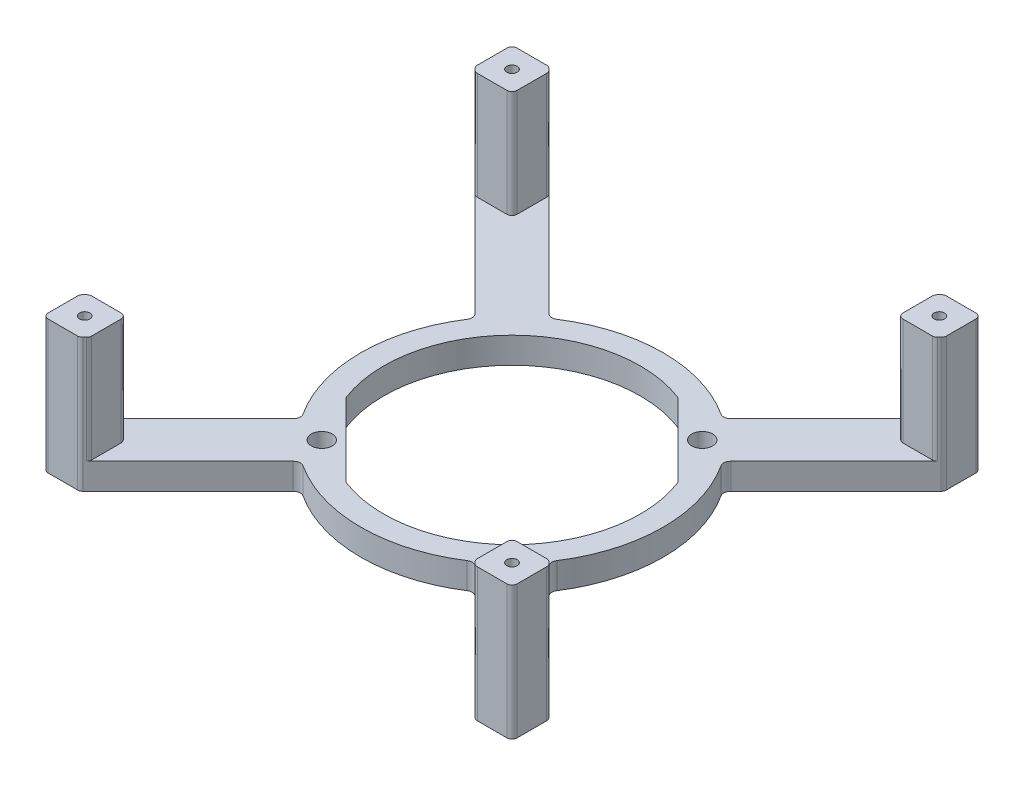
SolidWorks part; units mm, degrees
ref_plane "Front Plane" through (0, 0, 0) normal (0, 0, 1) x (1, 0, 0)
ref_plane "Top Plane" through (0, 0, 0) normal (0, 1, 0) x (1, 0, 0)
ref_plane "Right Plane" through (0, 0, 0) normal (1, 0, 0) x (0, 0, -1)
sketch "Sketch1" plane through (0, 0, 0) normal (0, 1, 0) x (1, 0, 0)
  line L0 (0, 50) -> (100, 50) construction
  line L1 (0, 0) -> (100, 0) construction
  line L2 (0, 0) -> (0, 100) construction
  line L3 (0, 100) -> (100, 100) construction
  line L4 (100, 0) -> (100, 100) construction
  line L5 (50, 0) -> (50, 50) construction
  line L6 (50, 50) -> (50, 100) construction
  line L7 (6, 95) -> (11.6569, 95)
  line L8 (5, 95) -> (95, 95) construction
  line L9 (50, 50) -> (110.8194, 110.8194) construction
  line L10 (50, 50) -> (-8.0727, 108.0727) construction
  line L11 (72.981, 58.8388) -> (58.8388, 72.981)
  line L12 (41.1612, 27.019) -> (27.019, 41.1612)
  line L13 (5, 95) -> (5, 5) construction
  line L14 (5, 5) -> (95, 5) construction
  line L15 (95, 95) -> (95, 5) construction
  line L16 (12.364, 94.7071) -> (32.5387, 74.5324)
  line L17 (5, 94) -> (5, 88.3431)
  line L18 (5.2929, 87.636) -> (25.4676, 67.4613)
  line L19 (50, 50) -> (0, 0) construction
  line L20 (95, 94) -> (95, 88.3431)
  line L21 (94.7071, 87.636) -> (74.5324, 67.4613)
  line L22 (94, 95) -> (88.3431, 95)
  line L23 (87.636, 94.7071) -> (67.4613, 74.5324)
  line L24 (50, 50) -> (108.0727, 108.0727) construction
  line L25 (94, 5) -> (88.3431, 5)
  line L26 (87.636, 5.2929) -> (67.4613, 25.4676)
  line L27 (95, 6) -> (95, 11.6569)
  line L28 (94.7071, 12.364) -> (74.5324, 32.5387)
  line L29 (50, 50) -> (108.0727, -8.0727) construction
  line L30 (5, 6) -> (5, 11.6569)
  line L31 (5.2929, 12.364) -> (25.4676, 32.5387)
  line L32 (6, 5) -> (11.6569, 5)
  line L33 (12.364, 5.2929) -> (32.5387, 25.4676)
  line L34 (50, 50) -> (-8.0727, -8.0727) construction
  arc A0 (58.8388, 72.981) -> (27.019, 41.1612) centre (50, 50) ccw
  arc A1 (41.1612, 27.019) -> (72.981, 58.8388) centre (50, 50) ccw
  arc A2 (25.6492, 65.7492) -> (25.6492, 34.2508) centre (50, 50) ccw
  arc A3 (11.6569, 95) -> (12.364, 94.7071) centre (11.6569, 94) cw
  arc A4 (6, 95) -> (5, 94) centre (6, 94) ccw
  arc A5 (5, 88.3431) -> (5.2929, 87.636) centre (6, 88.3431) ccw
  arc A6 (95, 88.3431) -> (94.7071, 87.636) centre (94, 88.3431) cw
  arc A7 (95, 94) -> (94, 95) centre (94, 94) ccw
  arc A8 (88.3431, 95) -> (87.636, 94.7071) centre (88.3431, 94) ccw
  arc A9 (88.3431, 5) -> (87.636, 5.2929) centre (88.3431, 6) cw
  arc A10 (94, 5) -> (95, 6) centre (94, 6) ccw
  arc A11 (95, 11.6569) -> (94.7071, 12.364) centre (94, 11.6569) ccw
  arc A12 (5, 11.6569) -> (5.2929, 12.364) centre (6, 11.6569) cw
  arc A13 (5, 6) -> (6, 5) centre (6, 6) ccw
  arc A14 (11.6569, 5) -> (12.364, 5.2929) centre (11.6569, 6) ccw
  arc A15 (65.7492, 74.3508) -> (34.2508, 74.3508) centre (50, 50) ccw
  arc A16 (74.3508, 34.2508) -> (74.3508, 65.7492) centre (50, 50) ccw
  arc A17 (34.2508, 25.6492) -> (65.7492, 25.6492) centre (50, 50) ccw
  arc A18 (74.5324, 32.5387) -> (74.3508, 34.2508) centre (75.5007, 33.5071) cw
  arc A19 (67.4613, 25.4676) -> (65.7492, 25.6492) centre (66.4929, 24.4993) ccw
  arc A20 (32.5387, 25.4676) -> (34.2508, 25.6492) centre (33.5071, 24.4993) cw
  arc A21 (25.4676, 32.5387) -> (25.6492, 34.2508) centre (24.4993, 33.5071) ccw
  arc A22 (25.4676, 67.4613) -> (25.6492, 65.7492) centre (24.4993, 66.4929) cw
  arc A23 (32.5387, 74.5324) -> (34.2508, 74.3508) centre (33.5071, 75.5007) ccw
  arc A24 (74.5324, 67.4613) -> (74.3508, 65.7492) centre (75.5007, 66.4929) ccw
  arc A25 (67.4613, 74.5324) -> (65.7492, 74.3508) centre (66.4929, 75.5007) cw
  point P27 (12.0711, 95)
  point P33 (5, 87.9289)
  point P72 (50, 50)
  point P86 (31.7496, 31.7496)
  point P87 (68.2504, 68.2504)
  dimension "D3" = 58
  dimension "D5" = 45
  dimension "D12" = 1
  dimension "D16" = 1.3694
  dimension "D1" = 100
  dimension "D2" = 100
  dimension "D4" = 5
  dimension "D6" = 45
  dimension "D7" = 5
  dimension "D8" = 20
  dimension "D9" = 10
  dimension "D10" = 22.5
  dimension "D11" = 5
  dimension "D13" = 10
  dimension "D14" = 5
  dimension "D17" = 25.81
  dimension "D15" = 4
extrude "Boss-Extrude1" add sketch "Sketch1" along normal blind 5
sketch "Sketch4" plane through (0, 5, 0) normal (0, 1, 0) x (1, 0, 0)
  line L0 (5.2929, 94.7071) -> (94.7071, 5.2929) construction
  line L1 (5.2929, 5.2929) -> (94.7071, 94.7071) construction
  arc A0 (94, 5) -> (95, 6) centre (94, 6) ccw construction
  arc A1 (6, 95) -> (5, 94) centre (6, 94) ccw construction
  arc A3 (5, 6) -> (6, 5) centre (6, 6) ccw construction
  arc A4 (95, 94) -> (94, 95) centre (94, 94) ccw construction
  point P3 (50, 50)
  point P17 (31.7496, 31.7496)
  point P18 (68.2504, 68.2504)
  dimension "D1" = 25.81
  dimension "D2" = 0
hole_wizard "Tap Drill for M4x0.7 Tap1" positions "3DSketch2" profile "Sketch5" hole size "M4x0.7" standard "ANSI Metric" end condition through all
sketch3d "3DSketch2"
  point P0 (31.7496, 5, -31.7496)
  point P3 (68.2504, 5, -68.2504)
sketch "Sketch5" plane through (31.7496, 5, -31.7496) normal (1, 0, 0) x (0, 0, 1)
  line L0 (0, 0) -> (0, 5)
  line L1 (0, 5) -> (2, 5)
  line L2 (2, 5) -> (2, 0)
  line L5 (2, 0) -> (0, 0)
  line L11 (0, -6.35) -> (0, 107.95) construction
  dimension "Thru Hole Dia." = 4
  dimension "Thru Hole Depth" = 5
sketch "Sketch6" plane through (0, 5, 0) normal (0, 1, 0) x (1, 0, 0)
  line L1 (6, 95) -> (11.6569, 95)
  line L2 (5, 94) -> (5, 88.3431)
  line L5 (11.6569, 95) -> (6, 95) construction
  line L6 (5, 94) -> (5, 88.3431) construction
  line L7 (13, 93.6569) -> (13, 88)
  line L8 (12, 87) -> (6.3431, 87)
  line L9 (5.636, 87.2929) -> (5.2929, 87.636)
  line L10 (5.2929, 87.636) -> (25.4676, 67.4613) construction
  line L11 (12.7071, 94.364) -> (12.364, 94.7071)
  line L12 (32.5387, 74.5324) -> (12.364, 94.7071) construction
  arc A0 (5.2929, 87.636) -> (5, 88.3431) centre (6, 88.3431) cw
  arc A1 (5.636, 87.2929) -> (6.3431, 87) centre (6.3431, 88) ccw
  arc A2 (13, 88) -> (12, 87) centre (12, 88) cw
  arc A3 (12.7071, 94.364) -> (13, 93.6569) centre (12, 93.6569) cw
  arc A4 (12.364, 94.7071) -> (11.6569, 95) centre (11.6569, 94) ccw
  arc A5 (6, 95) -> (5, 94) centre (6, 94) ccw
  point P18 (5.9289, 87)
  point P23 (13, 94.0711)
  dimension "D5" = 1
  dimension "D1" = 0
  dimension "D2" = 0
  dimension "D3" = 8
  dimension "D4" = 8
extrude "Boss-Extrude2" add sketch "Sketch6" along normal blind 20.6
sketch "Sketch7" plane through (0, 25.6, 0) normal (0, 1, 0) x (1, 0, 0)
  line L0 (5.2929, 94.7071) -> (94.7071, 5.2929) construction
  line L1 (5, 94) -> (5, 88.3431) construction
  point P0 (9, 91)
  dimension "D1" = 4
hole_wizard "Tap Drill for M2x0.4 Tap1" positions "3DSketch3" profile "Sketch9" hole size "M2x0.4" standard "ANSI Metric"
sketch3d "3DSketch3"
  point P0 (9, 25.6, -91)
sketch "Sketch9" plane through (9, 25.6, -91) normal (1, 0, 0) x (0, 0, 1)
  line L0 (0, 0) -> (0, 4.6009)
  line L1 (0, 4.6009) -> (1, 4)
  line L2 (1, 4) -> (1, 0)
  line L5 (1, 0) -> (0, 0)
  line L10 (0, 4.6009) -> (-1, 4) construction
  line L11 (0, -6.35) -> (0, 107.95) construction
  dimension "Hole Dia." = 2
  dimension "Hole Depth" = 4
  dimension "Drill Angle" = 118
ref_axis "Axis1" through (50, 5, -50) along (0, -1, 0)
pattern_circular "CirPattern1" count 4 every 90 about axis through (50, 5, -50) along (0, -1, 0) of "Boss-Extrude2", "Tap Drill for M2x0.4 Tap1"
